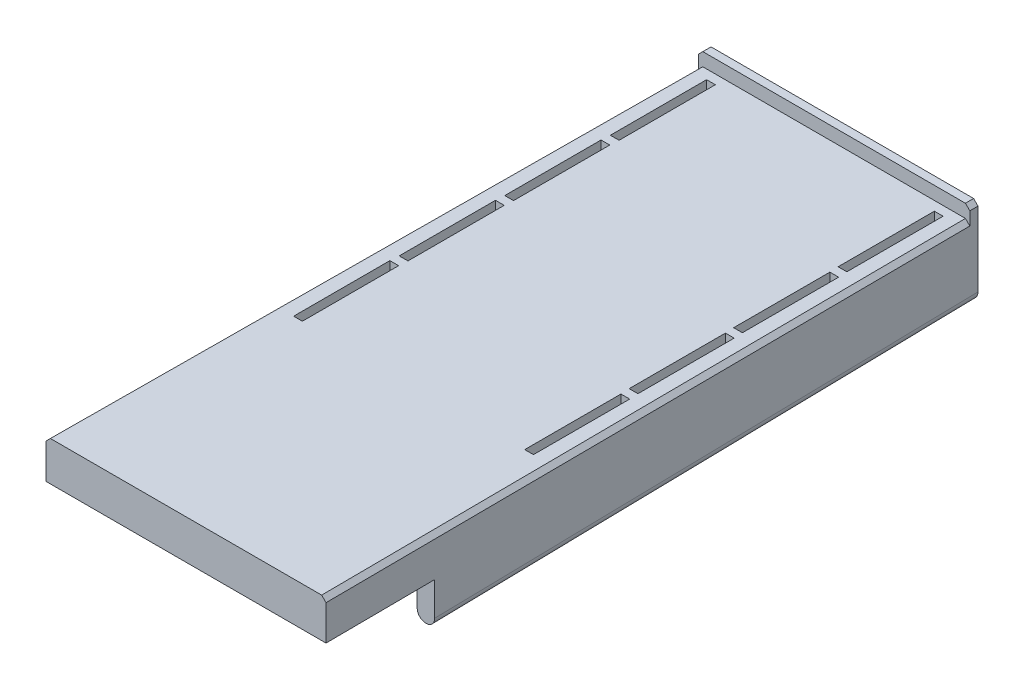
SolidWorks part; units mm, degrees
ref_plane "Front Plane" through (0, 0, 0) normal (0, 0, 1) x (1, 0, 0)
ref_plane "Top Plane" through (0, 0, 0) normal (0, 1, 0) x (1, 0, 0)
ref_plane "Right Plane" through (0, 0, 0) normal (1, 0, 0) x (0, 0, -1)
sketch "Sketch1" plane through (0, 0, 0) normal (0, 1, 0) x (1, 0, 0)
  line L0 (31, 0) -> (-31, 0)
  line L1 (0, 0) -> (0, -150) construction
  line L2 (32, -150) -> (-32, -150)
  line L3 (-32, -150) -> (-31, 0)
  line L4 (32, -150) -> (31, 0)
  dimension "\"neck length" = 150
extrude "Boss-Extrude1" add sketch "Sketch1" along normal blind 19
sketch "Sketch4" plane through (0, 0, 0) normal (1, 0, 0) x (0, 0, -1)
  line L0 (-150, 0) -> (0, 0)
  line L1 (0, 0) -> (0, 2)
  line L2 (0, 19) -> (0, 0) construction
  line L4 (0, 2) -> (-150, 0)
extrude "Cut-Extrude1" cut sketch "Sketch4" against normal through all both and the other way through all
shell "Shell1" thickness 4 removed face at (0, 1, 75)
fillet "Fillet2" 2 edges at (31.5, 1, 75) (27.4999, 1, 75) type full round first side face at (31.5, 10, 75) second side face at (27.4999, 5.5, 75) middle face at (0, 1, 75)
fillet "Fillet3" 2 edges at (-31.5, 1, 75) (-27.4999, 1, 75) type full round first side face at (-31.5, 10, 75) second side face at (-27.4999, 5.5, 75) middle face at (0.0001, 1, 75)
sketch "Sketch5" plane through (0, 19, 0) normal (0, 1, 0) x (1, 0, 0)
  line L0 (-31, 0) -> (-31.0125, -1.8797)
  line L1 (-31, 0) -> (-32, -150) construction
  line L2 (-31.0125, -1.8797) -> (31.0125, -1.8797)
  line L3 (32, -150) -> (31, 0) construction
  line L4 (31.0125, -1.8797) -> (31, 0)
  line L5 (31, 0) -> (-31, 0)
extrude "Boss-Extrude2" add sketch "Sketch5" along normal blind 3
chamfer "Chamfer1" distance 1 angle 45 2 edges at (31.5063, 19, 75.9398) (-31.5063, 19, 75.9398)
chamfer "Chamfer2" distance 1 angle 45 2 edges at (31.0063, 22, 0.9398) (-31.0063, 22, 0.9398)
sketch "Sketch6" plane through (0, 19, 0) normal (0, 1, 0) x (1, 0, 0)
  line L0 (-30.0125, -1.8797) -> (30.0125, -1.8797)
  line L1 (0, -1.8797) -> (0, -197.9912) construction
  line L2 (-31.316, -197.3975) -> (31.316, -197.3975)
  line L3 (31, -150) -> (30.0125, -1.8797) construction
  line L4 (31.316, -197.3975) -> (30.0125, -1.8797)
  line L5 (-30.0125, -1.8797) -> (-31.316, -197.3975)
  line L6 (-30.0125, -1.8797) -> (-31, -150) construction
extrude "Cut-Extrude2" [suppressed] cut sketch "Sketch6" against normal blind 1.6
sketch "Sketch7" plane through (0, 0, 150) normal (0, 0, 1) x (1, 0, 0)
  line L1 (-32, 10) -> (32, 10)
  line L2 (-32, 18) -> (-32, 2) construction
  line L3 (32, 18) -> (32, 2) construction
  line L4 (32, 10) -> (32, 0)
  line L7 (-32, 0) -> (-32, 10)
  line L8 (-32, 0) -> (32, 0)
extrude "Cut-Extrude3" cut sketch "Sketch7" against normal blind 25
sketch "Sketch11" plane through (0, 10, 0) normal (0, -1, 0) x (1, 0, 0)
  line L0 (27.1522, 27.9997) -> (27.1522, 49.9997)
  line L1 (27.0266, 4) -> (25.0266, 4)
  line L2 (27.0266, 4) -> (27.0266, 26)
  line L3 (27.0266, 26) -> (25.0266, 26)
  line L4 (25.0266, 4) -> (25.0266, 26)
  line L5 (27.1522, 27.9997) -> (25.1522, 27.9997)
  line L6 (25.1522, 27.9997) -> (25.1522, 49.9997)
  line L7 (27.1522, 49.9997) -> (25.1522, 49.9997)
  line L8 (27.2779, 51.9993) -> (27.2779, 73.9993)
  line L9 (27.2779, 51.9993) -> (25.2779, 51.9993)
  line L10 (25.2779, 51.9993) -> (25.2779, 73.9993)
  line L11 (27.2779, 73.9993) -> (25.2779, 73.9993)
  line L12 (27.4036, 75.999) -> (27.4036, 97.999)
  line L13 (27.4036, 75.999) -> (25.4036, 75.999)
  line L14 (25.4036, 75.999) -> (25.4036, 97.999)
  line L15 (27.4036, 97.999) -> (25.4036, 97.999)
  line L16 (27.0266, 4) -> (27.1522, 27.9997) construction
  line L17 (0, -11.9167) -> (0, 11.9167) construction
  line L18 (-27.4036, 75.999) -> (-25.4036, 75.999)
  line L19 (-25.4036, 75.999) -> (-25.4036, 97.999)
  line L20 (-27.4036, 97.999) -> (-25.4036, 97.999)
  line L21 (-27.4036, 75.999) -> (-27.4036, 97.999)
  line L22 (-27.2779, 51.9993) -> (-25.2779, 51.9993)
  line L23 (-25.2779, 51.9993) -> (-25.2779, 73.9993)
  line L24 (-27.2779, 73.9993) -> (-25.2779, 73.9993)
  line L25 (-27.2779, 51.9993) -> (-27.2779, 73.9993)
  line L26 (-27.1522, 27.9997) -> (-25.1522, 27.9997)
  line L27 (-25.1522, 27.9997) -> (-25.1522, 49.9997)
  line L28 (-27.1522, 49.9997) -> (-25.1522, 49.9997)
  line L29 (-27.1522, 27.9997) -> (-27.1522, 49.9997)
  line L30 (-27.0266, 26) -> (-25.0266, 26)
  line L31 (-25.0266, 4) -> (-25.0266, 26)
  line L32 (-27.0266, 4) -> (-25.0266, 4)
  line L33 (-27.0266, 4) -> (-27.0266, 26)
  line L34 (27.1522, -95.0215) -> (27.1522, -73.0215)
  line L35 (-25.0266, -119.0211) -> (-25.0266, -97.0211)
  line L36 (-27.1522, -73.0215) -> (-25.1522, -73.0215)
  line L37 (27.0266, -119.0211) -> (25.0266, -119.0211)
  line L38 (27.0266, -97.0211) -> (25.0266, -97.0211)
  line L39 (27.4036, -47.0221) -> (25.4036, -47.0221)
  line L40 (-27.4036, -47.0221) -> (-25.4036, -47.0221)
  line L41 (27.4036, -25.0221) -> (25.4036, -25.0221)
  line L42 (27.1522, -73.0215) -> (25.1522, -73.0215)
  line L43 (-27.4036, -25.0221) -> (-25.4036, -25.0221)
  line L44 (-27.0266, -119.0211) -> (-27.0266, -97.0211)
  line L45 (27.0266, -119.0211) -> (27.0266, -97.0211)
  line L46 (25.0266, -119.0211) -> (25.0266, -97.0211)
  line L47 (27.2779, -49.0218) -> (25.2779, -49.0218)
  line L48 (27.2779, -71.0218) -> (25.2779, -71.0218)
  line L49 (-25.4036, -47.0221) -> (-25.4036, -25.0221)
  line L50 (25.1522, -95.0215) -> (25.1522, -73.0215)
  line L51 (-27.4036, -47.0221) -> (-27.4036, -25.0221)
  line L52 (-25.2779, -71.0218) -> (-25.2779, -49.0218)
  line L53 (-25.1522, -95.0215) -> (-25.1522, -73.0215)
  line L54 (-27.0266, -97.0211) -> (-25.0266, -97.0211)
  line L55 (-27.0266, -119.0211) -> (-25.0266, -119.0211)
  line L56 (-27.2779, -49.0218) -> (-25.2779, -49.0218)
  line L57 (27.1522, -95.0215) -> (25.1522, -95.0215)
  line L58 (27.4036, -47.0221) -> (27.4036, -25.0221)
  line L59 (27.2779, -71.0218) -> (27.2779, -49.0218)
  line L60 (-27.2779, -71.0218) -> (-25.2779, -71.0218)
  line L61 (-27.2779, -71.0218) -> (-27.2779, -49.0218)
  line L62 (25.2779, -71.0218) -> (25.2779, -49.0218)
  line L63 (25.4036, -47.0221) -> (25.4036, -25.0221)
  line L64 (-27.1522, -95.0215) -> (-25.1522, -95.0215)
  line L65 (-27.1522, -95.0215) -> (-27.1522, -73.0215)
  dimension "D1" = 22
  dimension "D2" = 2
  dimension "D4" = 24
  dimension "D3" = 4
extrude "Cut-Extrude4" cut sketch "Sketch11" against normal through all
equation "\"neck length\"= 200mm"
